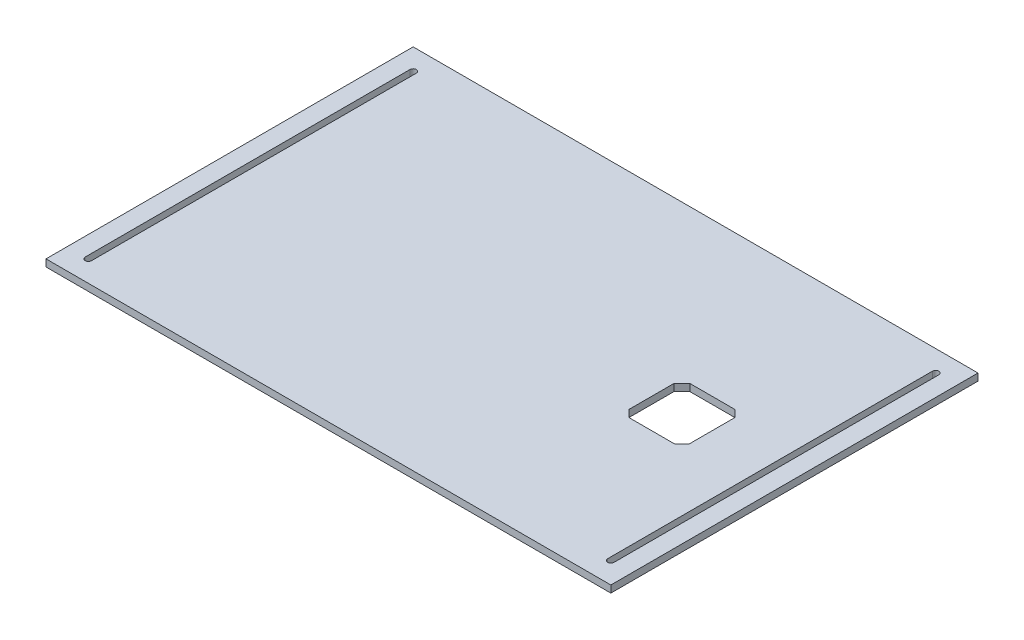
SolidWorks part; units mm, degrees
ref_plane "前基準面" through (0, 0, 0) normal (0, 0, 1) x (1, 0, 0)
ref_plane "上基準面" through (0, 0, 0) normal (0, 1, 0) x (1, 0, 0)
ref_plane "右基準面" through (0, 0, 0) normal (1, 0, 0) x (0, 0, -1)
sketch "草圖1" plane through (0, 0, 0) normal (0, 1, 0) x (1, 0, 0)
  line L0 (200, 60) -> (170, 60) construction
  line L1 (200, 160) -> (-200, 160) construction
  line L2 (200, 160) -> (200, -160) construction
  line L3 (200, -160) -> (-200, -160) construction
  line L4 (-200, 160) -> (-200, -160) construction
  line L5 (0, -160) -> (0, 160) construction
  line L6 (200, 0) -> (-200, 0) construction
  line L7 (-200, 160) -> (200, 160) construction
  line L8 (-200, 160) -> (-200, 130) construction
  line L9 (-200, 130) -> (200, 130) construction
  line L10 (200, 160) -> (200, 130) construction
  line L11 (-200, 130) -> (-170, 130) construction
  line L12 (-200, 130) -> (-200, -130) construction
  line L13 (-200, -130) -> (-170, -130) construction
  line L14 (-170, 130) -> (-170, -130) construction
  line L15 (200, -160) -> (-200, -160) construction
  line L16 (200, -160) -> (200, -130) construction
  line L17 (200, -130) -> (-200, -130) construction
  line L18 (-200, -160) -> (-200, -130) construction
  line L19 (200, -130) -> (170, -130) construction
  line L20 (200, -130) -> (200, 130) construction
  line L21 (200, 130) -> (170, 130) construction
  line L22 (170, -130) -> (170, 130) construction
  line L23 (-200, 130) -> (-170, 130) construction
  line L24 (-200, 130) -> (-200, 60) construction
  line L25 (-200, 60) -> (-170, 60) construction
  line L26 (-170, 130) -> (-170, 60) construction
  line L27 (170, 130) -> (170, 60) construction
  line L29 (200, 130) -> (200, 60) construction
  line L30 (-200, -60) -> (-170, -60) construction
  line L31 (-170, -130) -> (-170, -60) construction
  line L32 (-200, -130) -> (-170, -130) construction
  line L33 (-200, -130) -> (-200, -60) construction
  line L34 (200, -130) -> (200, -60) construction
  line L35 (170, -130) -> (170, -60) construction
  line L36 (200, -60) -> (170, -60) construction
  line L37 (200, -130) -> (170, -130) construction
  line L40 (-200, 130) -> (-200, -130)
  line L42 (200, 130) -> (200, -130)
  line L43 (-200, 130) -> (200, 130)
  line L44 (-200, 130) -> (-200, -130)
  line L45 (-200, -130) -> (200, -130)
  line L46 (200, 130) -> (200, -130)
  point P0 (0, 0)
  dimension "D1" = 400
  dimension "D2" = 320
  dimension "D4" = 30
  dimension "D6" = 30
  dimension "D7" = 70
extrude "填料-伸長1" add sketch "草圖1" along normal blind 5 contours L40 L45 L42 L43 region at (0, 0, 0)
sketch "草圖2" plane through (0, 5, 0) normal (0, 1, 0) x (1, 0, 0)
  line L0 (-185, 130) -> (-185, -130) construction
  line L1 (-200, 130) -> (200, 130) construction
  line L2 (-200, -130) -> (200, -130) construction
  line L3 (185, -130) -> (185, 130) construction
  line L4 (-185, 115) -> (-185, -115) construction
  line L5 (-182.75, 115) -> (-182.75, -115)
  line L6 (-187.25, 115) -> (-187.25, -115)
  line L7 (-200, 60) -> (-170, 60) construction
  line L8 (200, 0) -> (-200, 0) construction
  line L9 (0, -160) -> (0, 160) construction
  line L10 (0, -160) -> (0, 160) construction
  line L11 (185, 115) -> (185, -115) construction
  line L12 (182.75, 115) -> (182.75, -115)
  line L13 (187.25, 115) -> (187.25, -115)
  arc A0 (-182.75, 115) -> (-187.25, 115) centre (-185, 115) ccw
  arc A1 (-187.25, -115) -> (-182.75, -115) centre (-185, -115) ccw
  arc A2 (182.75, 115) -> (187.25, 115) centre (185, 115) cw
  arc A3 (187.25, -115) -> (182.75, -115) centre (185, -115) cw
  point P10 (-185, 0)
  point P17 (-185, 60)
  point P25 (185, 0)
  dimension "D1" = 4.5
  dimension "D2" = 230
extrude "除料-伸長1" cut sketch "草圖2" against normal through all
sketch "草圖3" plane through (0, 5, 0) normal (0, 1, 0) x (1, 0, 0)
  line L0 (200, 0) -> (-200, 0) construction
  line L1 (104.4, 21.575) -> (136.25, 21.575)
  line L2 (98.75, 15.925) -> (98.75, -15.925)
  line L3 (103.75, -20.925) -> (136.25, -20.925)
  line L4 (141.25, 16.575) -> (141.25, -15.925)
  line L5 (200, 130) -> (200, -130) construction
  line L6 (136.25, -20.925) -> (141.25, -15.925)
  line L7 (136.25, 21.575) -> (141.25, 16.575)
  line L8 (98.75, 15.925) -> (104.4, 21.575)
  line L9 (98.75, -15.925) -> (103.75, -20.925)
  line L10 (200, 130) -> (200, -130) construction
  circle A0 centre (103.75, 16.015) radius 1.75 construction
  circle A1 centre (134.75, 16.015) radius 1.75 construction
  circle A2 centre (134.75, -14.985) radius 1.75 construction
  circle A3 centre (103.75, -14.985) radius 1.75 construction
  point P0 (98.75, 21.575)
  point P1 (141.25, -20.925)
  point P2 (98.75, -20.925)
  point P3 (141.25, 21.575)
  point P8 (120, 0)
  point P25 (0, 0)
  point P28 (0, 0)
  point P29 (0, 0)
  point P30 (0, 0)
  point P31 (98.75, 0)
  point P32 (0, 0)
  point P33 (120, -20.925)
  dimension "D2" = 3.5
  dimension "D10" = 42.5
  dimension "D1" = 42.5
  dimension "D3" = 5.56
  dimension "D4" = 5
  dimension "D7" = 31
  dimension "D8" = 31
  dimension "D9" = 80
  dimension "D11" = 80
  dimension "D5" = 2
  dimension "D6" = 2
extrude "除料-伸長2" cut sketch "草圖3" against normal through all
